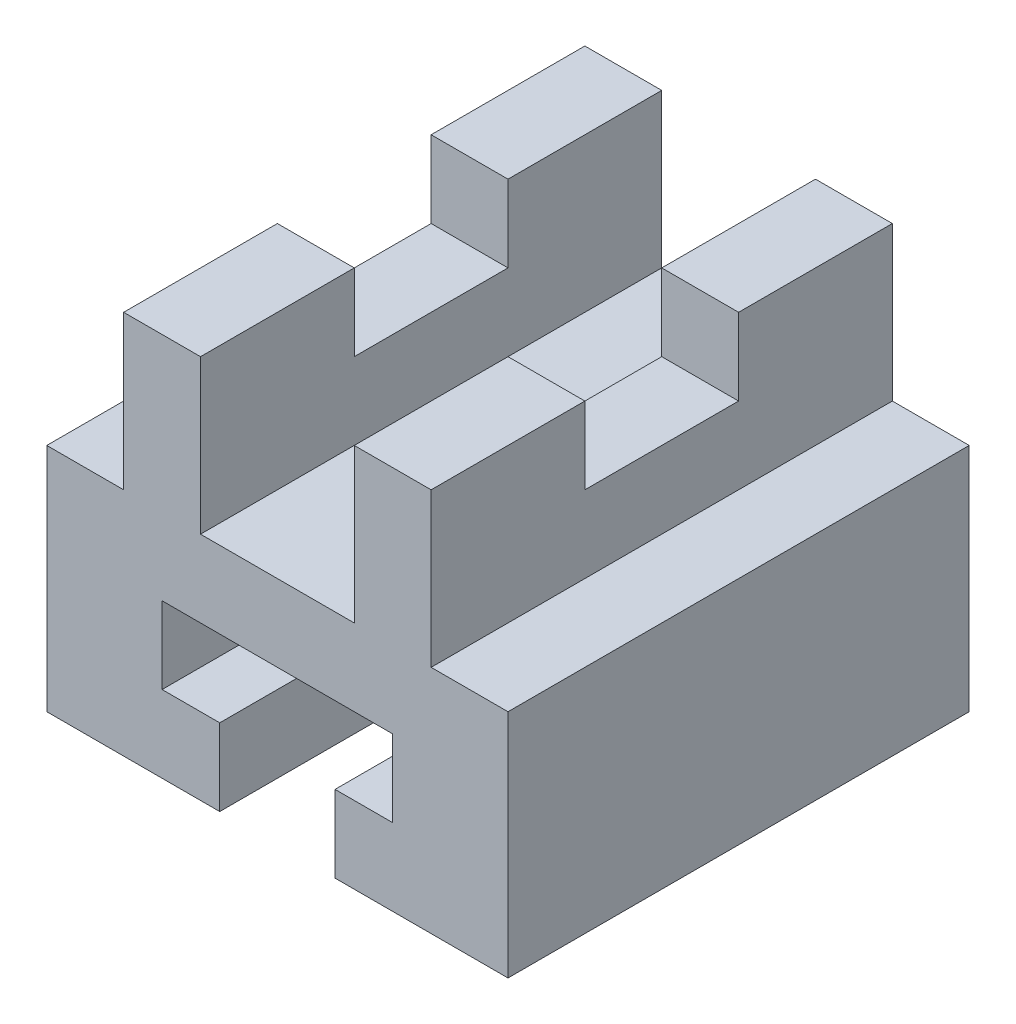
SolidWorks part; units mm, degrees
ref_plane "Front" through (0, 0, 0) normal (0, 0, 1) x (1, 0, 0)
ref_plane "Top" through (0, 0, 0) normal (0, 1, 0) x (1, 0, 0)
ref_plane "Right" through (0, 0, 0) normal (1, 0, 0) x (0, 0, -1)
ref_axis "Axis1" through (-84.4107, 0, 0) along (1, 0, 0)
ref_axis "Axis2" through (0, 64.3378, 0) along (0, -1, 0)
ref_axis "Axis3" through (0, 0, -102.329) along (0, 0, 1)
sketch "Sketch1" plane through (0, 0, 0) normal (0, 0, 1) x (1, 0, 0)
  line L0 (-20.3461, 0) -> (9.6539, 0)
  line L1 (9.6539, 0) -> (9.6539, -10)
  line L2 (9.6539, -10) -> (2.1539, -10)
  line L3 (2.1539, -10) -> (2.1539, -20)
  line L4 (2.1539, -20) -> (24.6539, -20)
  line L5 (24.6539, -20) -> (24.6539, 10)
  line L6 (24.6539, 10) -> (14.6539, 10)
  line L7 (14.6539, 10) -> (14.6539, 30)
  line L8 (14.6539, 30) -> (4.6539, 30)
  line L9 (4.6539, 30) -> (4.6539, 10)
  line L10 (4.6539, 10) -> (-15.3461, 10)
  line L11 (-15.3461, 10) -> (-15.3461, 30)
  line L12 (-15.3461, 30) -> (-25.3461, 30)
  line L13 (-25.3461, 30) -> (-25.3461, 10)
  line L14 (-25.3461, 10) -> (-35.3461, 10)
  line L15 (-35.3461, 10) -> (-35.3461, -20)
  line L16 (-35.3461, -20) -> (-12.8461, -20)
  line L17 (-12.8461, -20) -> (-12.8461, -10)
  line L18 (-12.8461, -10) -> (-20.3461, -10)
  line L19 (-20.3461, -10) -> (-20.3461, 0)
  point P19 (0, 0)
  point P22 (0, 0)
  dimension "D1" = 15
  dimension "D2" = 30
  dimension "D3" = 10
  dimension "D4" = 10
  dimension "D5" = 50
  dimension "D6" = 50
  dimension "D7" = 20
  dimension "D8" = 20
  dimension "D9" = 10
  dimension "D10" = 10
  dimension "D11" = 20
  dimension "D12" = 10
  dimension "D14" = 15
extrude "Boss-Extrude1" add sketch "Sketch1" along normal blind 60
sketch "Sketch2" plane through (14.6539, 0, 0) normal (1, 0, 0) x (0, 0, -1)
  line L0 (-60, 30) -> (0, 30) construction
  line L1 (-20, 30) -> (-30, 30)
  line L2 (-30, 30) -> (-40, 30)
  line L3 (-40, 30) -> (-40, 20)
  line L4 (-40, 20) -> (-20, 20)
  line L5 (-20, 20) -> (-20, 30)
  dimension "D1" = 10
  dimension "D2" = 10
  dimension "D3" = 10
extrude "Cut-Extrude1" cut sketch "Sketch2" against normal through all
